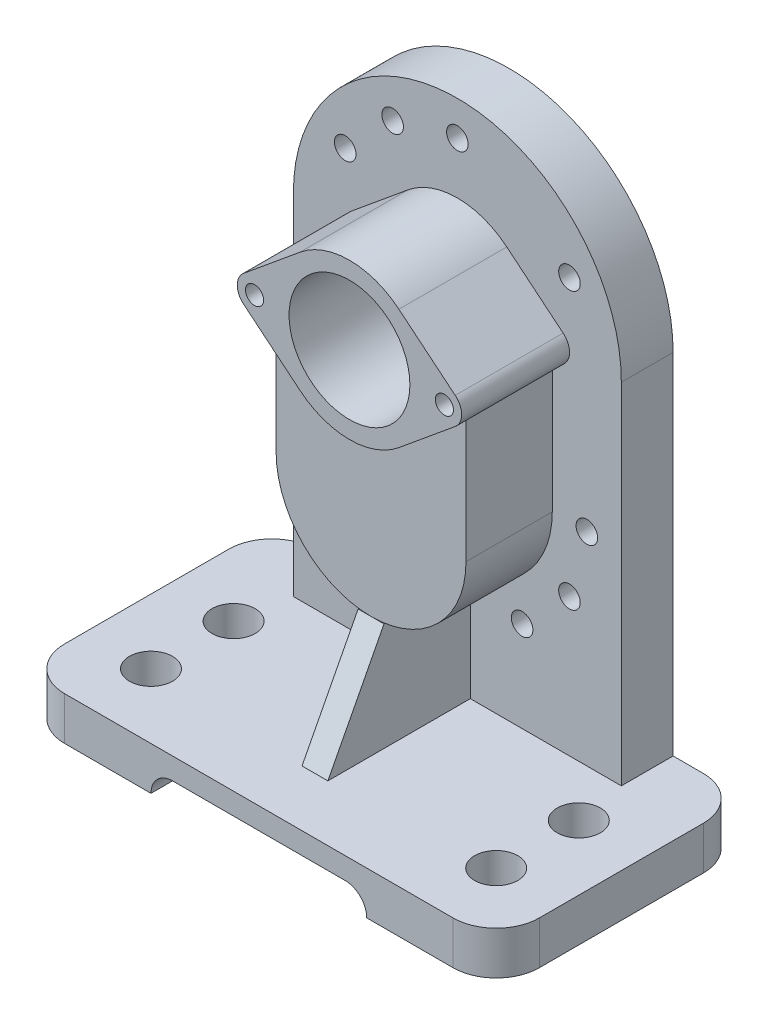
SolidWorks part; units mm, degrees
ref_plane "前视基准面" through (0, 0, 0) normal (0, 0, 1) x (1, 0, 0)
ref_plane "上视基准面" through (0, 0, 0) normal (0, 1, 0) x (1, 0, 0)
ref_plane "右视基准面" through (0, 0, 0) normal (1, 0, 0) x (0, 0, -1)
sketch "草图1" plane through (0, 0, 0) normal (0, 1, 0) x (1, 0, 0)
  line L0 (4.2318, 36.3629) -> (4.2318, -45.034) construction
  line L1 (-50.7682, 22.1966) -> (59.2318, 22.1966)
  line L2 (-50.7682, 22.1966) -> (-50.7682, -35.8034)
  line L3 (-50.7682, -35.8034) -> (59.2318, -35.8034)
  line L4 (59.2318, 22.1966) -> (59.2318, -35.8034)
  line L5 (-50.7682, -6.8034) -> (72.5859, -6.8034) construction
  circle A2 centre (44.2318, -20.8034) radius 5
  circle A3 centre (-35.7682, -20.8034) radius 5
  circle A4 centre (-35.7682, -1.6643) radius 5
  circle A5 centre (44.2318, -1.6643) radius 5
extrude "凸台-拉伸1" add sketch "草图1" along normal blind 10
sketch "草图2" plane through (0, 0, 35.8034) normal (0, 0, 1) x (1, 0, 0)
  line L0 (4.2318, 0.3671) -> (4.2318, 14.2993) construction
  line L3 (4.2318, 0) -> (4.2318, 5)
  line L4 (-50.7682, 0) -> (59.2318, 0) construction
  line L5 (4.2318, 5) -> (29.2318, 5)
  line L6 (29.2318, 5) -> (29.2318, 0)
  line L7 (29.2318, 0) -> (-20.7682, 0)
  line L8 (-20.7682, 0) -> (-20.7682, 5)
  line L9 (-20.7682, 5) -> (4.2318, 5)
  line M9 (-50.7682, 0) -> (59.2318, 0)
extrude "切除-拉伸1" cut sketch "草图2" against normal through all contours L9 L8 L3 M9 | L6 L5 L3 M9 region at (-8.2682, 2.5, 35.8034) region at (16.7318, 2.5, 35.8034)
fillet "圆角2" radius 5 2 edges at (29.2318, 5, 6.8034) (-20.7682, 5, 6.8034)
fillet "圆角3" radius 10 4 edges at (59.2318, 5, 35.8034) (59.2318, 5, -22.1966) (-50.7682, 5, -22.1966) (-50.7682, 5, 35.8034)
sketch "草图4" plane through (0, 0, -22.1966) normal (0, 0, -1) x (-1, 0, 0)
  line L0 (-4.2318, -3.0247) -> (-4.2318, 18.8945) construction
  line L2 (-49.2318, 10) -> (40.7682, 10) construction
  line L4 (-4.2318, 74) -> (31.924, 74) construction
  line L5 (-42.4668, 91) -> (28.5631, 91) construction
  line L6 (33.7682, 91) -> (33.7682, 10)
  line L7 (33.7682, 10) -> (-42.2318, 10)
  line L8 (-42.2318, 10) -> (-42.2318, 91)
  line L9 (-119.6871, 57) -> (57.3496, 57) construction
  line L12 (-34.2318, 91) -> (-34.2318, 57) construction
  line L13 (25.7682, 91) -> (25.7682, 57) construction
  line L14 (-4.2318, 91) -> (21.7489, 106) construction
  line L15 (-4.2318, 91) -> (10.7682, 116.9808) construction
  line L16 (-30.2126, 106) -> (-4.2318, 91) construction
  line L17 (-34.2318, 57) -> (-4.2318, 57)
  line L18 (-4.2318, 57) -> (-19.2318, 31.0192) construction
  line L19 (-30.2126, 42) -> (-4.2318, 57) construction
  line L20 (10.7682, 31.0192) -> (-4.2318, 57) construction
  line L21 (25.7682, 57) -> (-4.2318, 57) construction
  arc A0 (33.7682, 91) -> (-42.2318, 91) centre (-4.2318, 91) ccw
  arc A7 (25.7682, 91) -> (-34.2318, 91) centre (-4.2318, 91) ccw construction
  arc A8 (-34.2318, 57) -> (25.7682, 57) centre (-4.2318, 57) ccw construction
  circle A9 centre (-4.2318, 121) radius 2.5
  circle A10 centre (10.7682, 116.9808) radius 2.5
  circle A12 centre (-30.2126, 106) radius 2.5
  circle A13 centre (-34.2318, 57) radius 2.5
  circle A14 centre (-19.2318, 31.0192) radius 2.5
  circle A15 centre (-30.2126, 42) radius 2.5
  circle A16 centre (25.7682, 57) radius 2.5
  circle A17 centre (10.7682, 31.0192) radius 2.5
  circle A18 centre (21.7489, 106) radius 2.5
  line M2 (40.7682, 10) -> (-49.2318, 10)
  dimension "D2" = 17
  dimension "D3" = 60
  dimension "D5" = 60
  dimension "D7" = 30
  dimension "D1" = 64
  dimension "D4" = 17
  dimension "D6" = 30
  dimension "D8" = 30
extrude "凸台-拉伸2" add sketch "草图4" against normal blind 12 contours L6 A0 L8 A18 A17 A16 A15 A14 A13 A12 A10 A9 M2 region at (4.2057, 65.5654, -22.1966)
sketch "草图7" plane through (0, 0, -10.1966) normal (0, 0, 1) x (1, 0, 0)
  line L0 (-33.7682, 91) -> (42.2318, 91) construction
  line L1 (-33.7682, 57) -> (42.2318, 57) construction
  line L2 (-20.2682, 94.1225) -> (-7.2231, 104.8847)
  line L3 (-33.7682, 91) -> (-33.7682, 10) construction
  line L4 (42.2318, 10) -> (42.2318, 91) construction
  line L7 (28.7318, 94.1225) -> (15.6867, 104.8847)
  line L8 (28.7318, 87.8775) -> (15.6867, 77.1153)
  line L9 (-20.2682, 87.8775) -> (-7.2231, 77.1153)
  line L10 (26.2318, 85.815) -> (26.2318, 57)
  line L11 (-17.7682, 85.815) -> (-17.7682, 57)
  arc A0 (-17.7682, 57) -> (26.2318, 57) centre (4.2318, 57) ccw
  arc A2 (-7.2231, 77.1153) -> (15.6867, 77.1153) centre (4.2318, 91) ccw
  arc A6 (-20.2682, 94.1225) -> (-20.2682, 87.8775) centre (-17.7682, 91) ccw
  arc A7 (28.7318, 87.8775) -> (28.7318, 94.1225) centre (26.2318, 91) ccw
  circle A8 centre (4.2318, 91) radius 14
  arc A9 (15.6867, 104.8847) -> (-7.2231, 104.8847) centre (4.2318, 91) ccw
extrude "凸台-拉伸14" add sketch "草图7" along normal blind 20 contours A2 L9 L11 A0 L10 L8 region at (4.2318, 58.6294, -10.1966)
sketch "草图8" plane through (0, 0, -22.1966) normal (0, 0, -1) x (-1, 0, 0)
  line L0 (-42.2318, 91) -> (33.7682, 91) construction
  line L1 (-42.2318, 57) -> (33.7682, 57) construction
  line L2 (-42.2318, 10) -> (-42.2318, 91) construction
  line L3 (33.7682, 91) -> (33.7682, 10) construction
  circle A0 centre (-4.2318, 57) radius 9
  circle A1 centre (-4.2318, 91) radius 9
hole_wizard "Ø18.0 (18) 直径孔1" positions "3D草图1" profile "草图9" hole size "Ø18.0" standard "GB"
sketch3d "3D草图1"
  point P0 (4.2318, 91, -22.1966)
  point P3 (4.2318, 57, -22.1966)
sketch "草图9" plane through (4.2318, 91, -22.1966) normal (1, 0, 0) x (0, 1, 0)
  line L0 (0, 0) -> (0, 20.4077)
  line L1 (0, 20.4077) -> (9, 15)
  line L2 (9, 15) -> (9, 0)
  line L5 (9, 0) -> (0, 0)
  line L10 (0, 20.4077) -> (-9, 15) construction
  line L11 (0, -6.35) -> (0, 107.95) construction
  dimension "孔直径" = 18
  dimension "孔深度" = 15
  dimension "导头角度" = 118
extrude "凸台-拉伸16" add sketch "草图7<3>" along normal blind 25 contours L7 A9 L2 A6 L9 A2 L8 A7 A8 region at (-13.3431, 99.0157, -10.1966)
sketch "草图7<3>" plane through (0, 0, -10.1966) normal (0, 0, 1) x (1, 0, 0) same geometry as "草图7"
sketch "草图18" plane through (0, 0, 14.8034) normal (0, 0, 1) x (1, 0, 0)
  circle A0 centre (-17.7682, 91) radius 2.5
  circle A1 centre (26.2318, 91) radius 2.5
hole_wizard "M5 螺纹孔1" positions "3D草图3" profile "草图19" tap size "M5" standard "GB"
sketch3d "3D草图3"
  point P0 (-17.7682, 91, 14.8034)
  point P3 (26.2318, 91, 14.8034)
sketch "草图19" plane through (-17.7682, 91, 14.8034) normal (1, 0, 0) x (0, -1, 0)
  line L0 (0, 0) -> (0, 16.2618)
  line L1 (0, 16.2618) -> (2.1, 15)
  line L2 (2.1, 15) -> (2.1, 0)
  line L5 (2.1, 0) -> (0, 0)
  line L10 (0, 16.2618) -> (-2.1, 15) construction
  line L11 (0, -6.35) -> (0, 107.95) construction
  dimension "螺纹孔钻头直径" = 4.2
  dimension "螺纹孔钻头深度" = 15
  dimension "导头角度" = 118
cosmetic thread "孔螺蚊线1" parameters "D1"=10, "D2"=5
cosmetic thread "孔螺蚊线2" parameters "D1"=10, "D2"=5
ref_plane "基准面3" through (4.2318, 0, 0) normal (1, 0, 0) x (0, 0, -1)
sketch "草图22" plane through (4.2318, 0, 0) normal (1, 0, 0) x (0, 0, -1)
  line L0 (-9.8034, 35) -> (10.1966, 35)
  line L1 (10.1966, 10) -> (10.1966, 91) construction
  line L2 (10.1966, 35) -> (10.1966, 10)
  line L3 (10.1966, 10) -> (-22.8034, 10)
  line L4 (-25.8034, 10) -> (12.1966, 10) construction
  line L5 (-22.8034, 10) -> (-9.8034, 35)
extrude "凸台-拉伸19" add sketch "草图22" along normal mid plane 6 separate body
